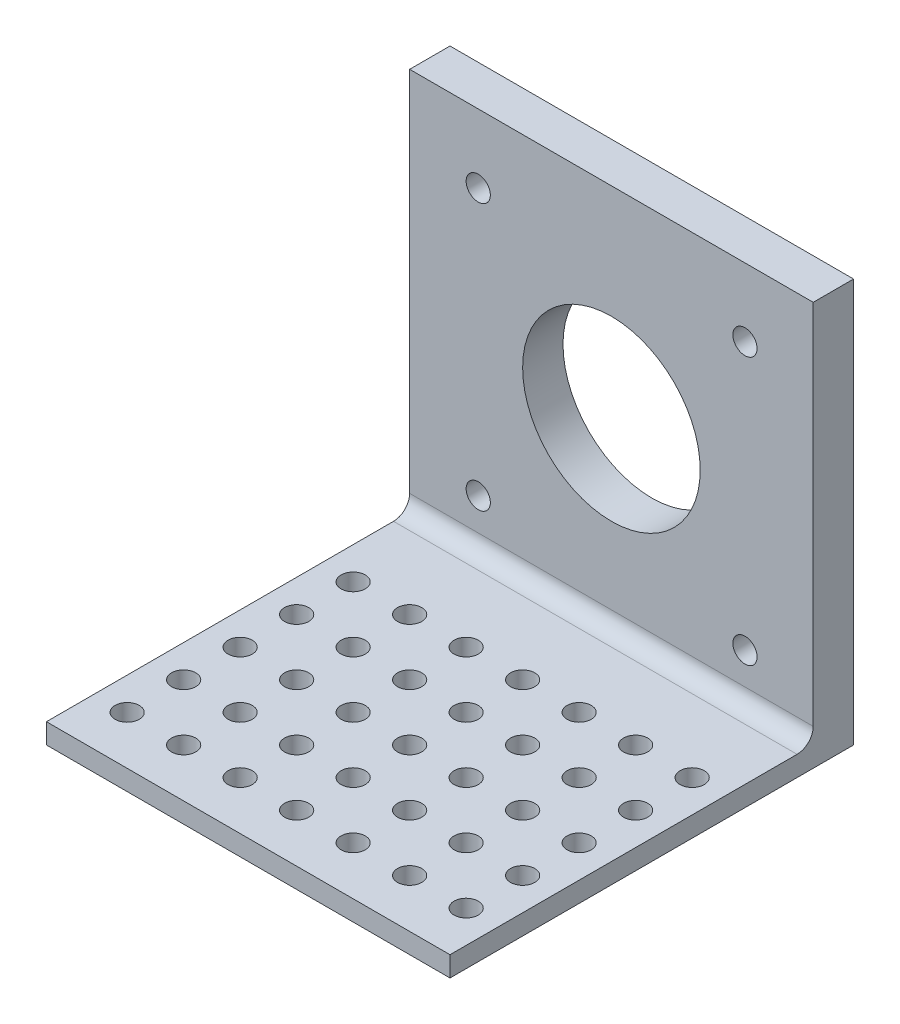
SolidWorks part; units mm, degrees
ref_plane "Plano frontal" through (0, 0, 0) normal (0, 0, 1) x (1, 0, 0)
ref_plane "Plano superior" through (0, 0, 0) normal (0, 1, 0) x (1, 0, 0)
ref_plane "Plano direito" through (0, 0, 0) normal (1, 0, 0) x (0, 0, -1)
sketch "Esboço1" plane through (0, 0, 0) normal (0, 0, 1) x (1, 0, 0)
  line L0 (0, 0) -> (50, -50) construction
  line L1 (0, 0) -> (50, 0)
  line L2 (0, 0) -> (0, -50)
  line L3 (0, -50) -> (50, -50)
  line L4 (50, 0) -> (50, -50)
  line L5 (0, -50) -> (50, 0) construction
  circle A0 centre (25, -25) radius 11
  circle A1 centre (8.5, -8.5) radius 1.5
  circle A2 centre (41.5465, -8.4535) radius 1.5
  circle A3 centre (41.5465, -41.5465) radius 1.5
  circle A4 centre (8.5, -41.5) radius 1.5
  dimension "D3" = 22
  dimension "D5" = 16.5
  dimension "D6" = 3
  dimension "D7" = 3
  dimension "D8" = 3
  dimension "D9" = 3
  dimension "D1" = 50
  dimension "D2" = 50
  dimension "D4" = 16.5
extrude "Ressalto-extrusão1" add sketch "Esboço1" along normal blind 10
sketch "Esboço2" plane through (0, 0, 0) normal (0, 0, 1) x (1, 0, 0)
  line L1 (0, -50) -> (50, -50)
  line L2 (50, -50) -> (50, -47.5)
  line L3 (50, -50) -> (50, 0) construction
  line L4 (50, -47.5) -> (0, -47.5)
  line L5 (0, 0) -> (0, -50) construction
  line L6 (0, -47.5) -> (0, -50)
  circle A0 centre (8.5, -41.5) radius 1.5 construction
  dimension "D1" = 6
  dimension "D2" = 2.5
extrude "Ressalto-extrusão2" add sketch "Esboço2" along normal blind 50
sketch "Esboço3" plane through (0, 0, 0) normal (0, 1, 0) x (1, 0, 0)
  line L0 (25, 0) -> (25, -50) construction
  line L1 (50, 0) -> (0, 0) construction
  line L2 (50, -50) -> (0, -50) construction
  line L3 (25, -50) -> (0, -50) construction
  line L4 (0, -50) -> (0, -10) construction
  line L5 (0, -50) -> (0, -30) construction
  line L6 (0, -30) -> (50, -30) construction
  line L7 (50, -50) -> (50, -10) construction
  line L8 (25, -30) -> (35, -30) construction
  line L9 (25, -30) -> (32, -30) construction
  line L10 (25, -30) -> (18, -30) construction
  line L11 (25, -30) -> (25, -37) construction
  line L12 (25, -30) -> (32, -30) construction
  line L13 (25, -30) -> (18, -30) construction
  circle A0 centre (25, -30) radius 1.5
  circle A1 centre (32, -30) radius 1.5
  circle A2 centre (39, -30) radius 1.5
  circle A3 centre (46, -30) radius 1.5
  circle A4 centre (32, -23) radius 1.5
  circle A5 centre (39, -23) radius 1.5
  circle A6 centre (46, -23) radius 1.5
  circle A7 centre (32, -16) radius 1.5
  circle A8 centre (39, -16) radius 1.5
  circle A9 centre (46, -16) radius 1.5
  circle A10 centre (25, -23) radius 1.5
  circle A11 centre (25, -16) radius 1.5
  circle A12 centre (18, -30) radius 1.5
  circle A13 centre (11, -30) radius 1.5
  circle A14 centre (4, -30) radius 1.5
  circle A15 centre (18, -37) radius 1.5
  circle A16 centre (11, -37) radius 1.5
  circle A17 centre (4, -37) radius 1.5
  circle A18 centre (18, -44) radius 1.5
  circle A19 centre (11, -44) radius 1.5
  circle A20 centre (4, -44) radius 1.5
  circle A21 centre (25, -37) radius 1.5
  circle A22 centre (25, -44) radius 1.5
  circle A23 centre (32, -30) radius 1.5
  circle A24 centre (39, -30) radius 1.5
  circle A25 centre (46, -30) radius 1.5
  circle A26 centre (32, -37) radius 1.5
  circle A27 centre (39, -37) radius 1.5
  circle A28 centre (46, -37) radius 1.5
  circle A29 centre (32, -44) radius 1.5
  circle A30 centre (39, -44) radius 1.5
  circle A31 centre (46, -44) radius 1.5
  circle A32 centre (25, -37) radius 1.5
  circle A33 centre (25, -44) radius 1.5
  circle A34 centre (18, -30) radius 1.5
  circle A35 centre (11, -30) radius 1.5
  circle A36 centre (4, -30) radius 1.5
  circle A37 centre (18, -23) radius 1.5
  circle A38 centre (11, -23) radius 1.5
  circle A39 centre (4, -23) radius 1.5
  circle A40 centre (18, -16) radius 1.5
  circle A41 centre (11, -16) radius 1.5
  circle A42 centre (4, -16) radius 1.5
  circle A43 centre (25, -23) radius 1.5
  circle A44 centre (25, -16) radius 1.5
  dimension "D1" = 3
  dimension "D4" = 10
  dimension "D5" = 7
  dimension "D8" = 7
  dimension "D9" = 7
  dimension "D12" = 7
  dimension "D15" = 7
  dimension "D6" = 4
  dimension "D7" = 3
  dimension "D10" = 4
  dimension "D11" = 3
  dimension "D2" = 4
  dimension "D3" = 3
  dimension "D13" = 4
  dimension "D14" = 3
extrude "Corte-extrusão1" cut sketch "Esboço3" against normal blind 101 contours A17 | A20 | A19 | A18 | A22 | A29 | A30 | A31 | A28 | A27 | A26 | A21 | A15 | A16 | A14 | A13 | A12 | A1 | A0 | A2 | A3 | A6 | A5 | A4 | A37 | A10 | A38 | A39 | A42 | A41 | A40 | A11 | A7 | A8 | A9 region at (4, 0, 37)
extrude "Ressalto-extrusão3" add sketch "Esboço1<2>" along normal blind 4
sketch "Esboço1<2>" plane through (0, 0, 0) normal (0, 0, 1) x (1, 0, 0) same geometry as "Esboço1"
ref_plane "Plano1" through (50, 0, 10) normal (0, 0, -1) x (-1, 0, 0)
sketch "Esboço5" plane through (0, 0, 0) normal (0, 1, 0) x (1, 0, 0)
  line L0 (50, -10) -> (50, 0) construction
  line L1 (0, -10) -> (50, -10)
  line L2 (0, -10) -> (0, -5)
  line L3 (0, -5) -> (50, -5)
  line L4 (50, -10) -> (50, -5)
extrude "Corte-extrusão2" cut sketch "Esboço5" against normal up to vertex (47.5 mm away) up to point (50, -47.5, 10)
fillet "Filete2" radius 2 1 edges at (25, -47.5, 5)
